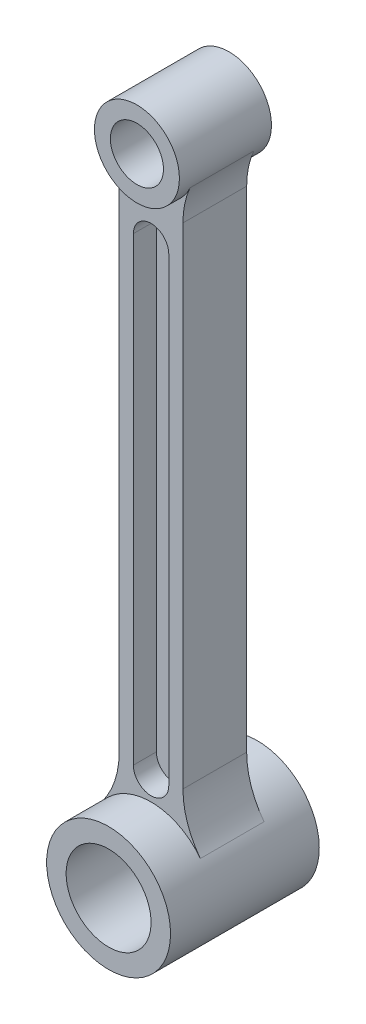
SolidWorks part; units mm, degrees
ref_plane "Front Plane" through (0, 0, 0) normal (1, 0, 0) x (0, 1, 0)
ref_plane "Top Plane" through (0, 0, 0) normal (0, 0, 1) x (0, 1, 0)
ref_plane "Right Plane" through (0, 0, 0) normal (0, 1, 0) x (-1, 0, 0)
sketch "Sketch1" plane through (0, 0, 0) normal (0, 0, 1) x (0, 1, 0)
  line L0 (0, 0) -> (16444.123, 0) construction
  line L1 (0, 0) -> (0, 16444.123) construction
  line L2 (25.1645, 9) -> (163.6125, 9)
  line L3 (25.1645, -9) -> (163.6125, -9)
  line L4 (24, 0) -> (154, 0) construction
  line L5 (24, 5) -> (154, 5)
  line L6 (24, -5) -> (154, -5)
  circle A0 centre (0, 0) radius 12
  circle A1 centre (0, 0) radius 17.5
  circle A2 centre (178, 0) radius 7.5
  circle A3 centre (178, 0) radius 12
  arc A4 (24, 5) -> (24, -5) centre (24, 0) ccw
  arc A5 (154, -5) -> (154, 5) centre (154, 0) ccw
  arc A6 (10.6115, 13.9157) -> (25.1645, 9) centre (25.1645, 33) ccw
  arc A7 (10.6115, -13.9157) -> (25.1645, -9) centre (25.1645, -33) cw
  arc A8 (163.6125, 9) -> (173.2042, 11) centre (163.6125, 33) ccw
  arc A9 (163.6125, -9) -> (173.2042, -11) centre (163.6125, -33) cw
  point P14 (89, 5)
  point P17 (89, 0)
  dimension "D1" = 35
  dimension "D2" = 24
  dimension "D3" = 24
  dimension "D4" = 15
  dimension "D9" = 89
  dimension "D10" = 24
  dimension "D11" = 24
  dimension "D5" = 178
  dimension "D6" = 130
  dimension "D7" = 18
  dimension "D8" = 10
extrude "Boss-Extrude1" add sketch "Sketch1" along normal mid plane 42 contours A1 A0 region at (-7.5441, 15.24, 0)
extrude "Boss-Extrude2" add sketch "Sketch1<3>" along normal mid plane 26 separate body contours A3 A2 region at (-9.7547, 184.3886, 0)
sketch "Sketch1<3>" plane through (0, 0, 0) normal (0, 0, 1) x (0, 1, 0) same geometry as "Sketch1"
extrude "Boss-Extrude3" add sketch "Sketch1<4>" along normal mid plane 18 contours L3 A9 A3 A8 L2 A6 A1 A7 A5 L6 A4 L5 region at (-7.3504, 94.3885, 0)
sketch "Sketch1<4>" plane through (0, 0, 0) normal (0, 0, 1) x (0, 1, 0) same geometry as "Sketch1"
extrude "Boss-Extrude4" add sketch "Sketch1<5>" along normal mid plane 5 contours L6 A5 L5 A4 region at (0, 89, 0)
sketch "Sketch1<5>" plane through (0, 0, 0) normal (0, 0, 1) x (0, 1, 0) same geometry as "Sketch1"
